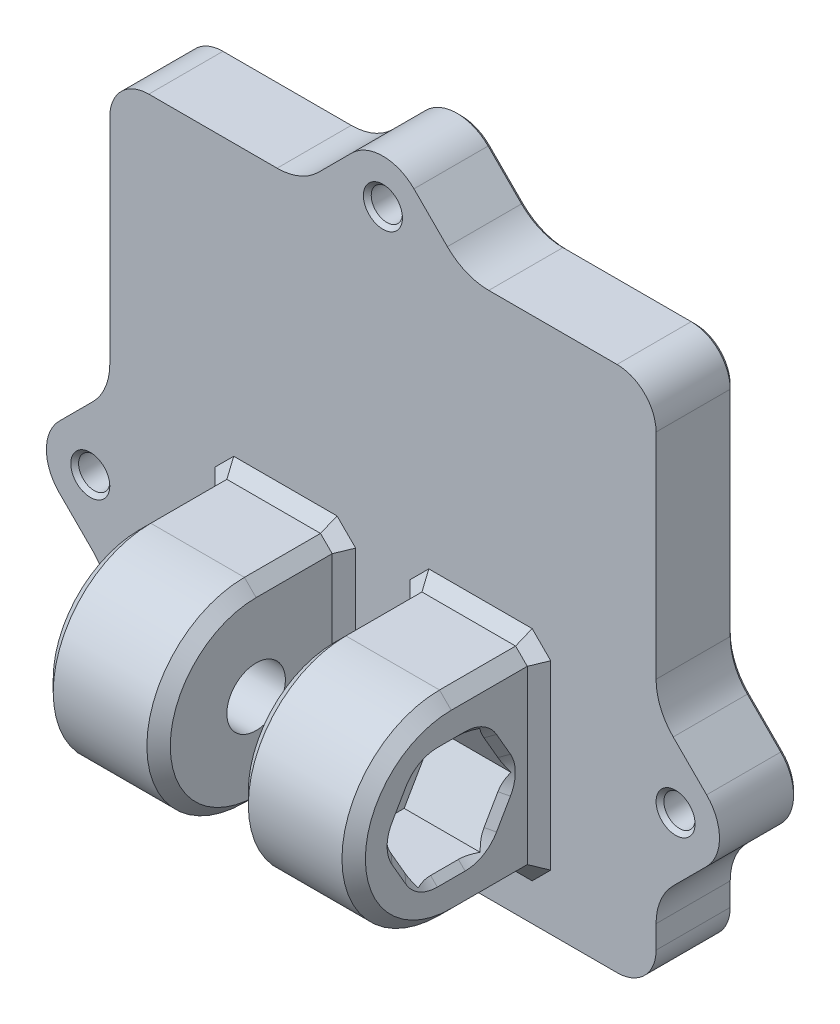
SolidWorks part; units mm, degrees
note: The reader was unsure of these and kept them because the rebuilt part matched: shared geometry of "Sketch13<3>", "Sketch17<3>", "Sketch17<4>", "Sketch17<5>", "Sketch17<6>".
material "POM Acetal Copolymer"
ref_plane "Front" through (0, 0, 0) normal (0, 0, 1) x (1, 0, 0)
ref_plane "Top" through (0, 0, 0) normal (0, 1, 0) x (1, 0, 0)
ref_plane "Right" through (0, 0, 0) normal (1, 0, 0) x (0, 0, -1)
sketch "Sketch13" plane through (0, 0, 0) normal (0, 0, 1) x (1, 0, 0)
  line L0 (-5.4246, -1) -> (-12, -1)
  line L1 (-14, -3) -> (-14, -13.9754)
  line L2 (-14, -24.8246) -> (-14, -26)
  line L3 (7.35, -3.5) -> (6.1644, -3.5) construction
  line L4 (7.75, -3.9) -> (7.75, -4.575) construction
  line L5 (-11.15, -28) -> (-11.15, -25.74) construction
  line L6 (-11.9, -24.5) -> (-11.9, -20.075) construction
  line L7 (-11.5, -19.675) -> (-10.35, -19.675) construction
  line L8 (-10.35, -14.475) -> (-11.5, -14.475) construction
  line L9 (-11.9, -14.075) -> (-11.9, -7.575) construction
  line L10 (-11.5, -7.175) -> (-10.65, -7.175) construction
  line L11 (7.35, -2.9) -> (6.1644, -2.9) construction
  line L12 (12, -28) -> (-12, -28)
  line L13 (1.591, 1.591) -> (3.3033, -0.1213)
  line L14 (-8.05, -3.9) -> (-8.05, -4.575) construction
  line L15 (0, 0) -> (0, -10) construction
  line L16 (-1.591, 1.591) -> (-3.3033, -0.1213)
  line L17 (11.5, -7.175) -> (10.35, -7.175) construction
  line L18 (11.9, -14.075) -> (11.9, -7.575) construction
  line L19 (10.15, -14.475) -> (11.5, -14.475) construction
  line L20 (11.5, -19.675) -> (10.15, -19.675) construction
  line L21 (11.9, -24.5) -> (11.9, -20.075) construction
  line L22 (11.15, -28) -> (11.15, -25.74) construction
  line L23 (10.5, -25.9) -> (-10.5, -25.9) construction
  line L24 (14, -24.8246) -> (14, -26)
  line L25 (14, -3) -> (14, -13.9754)
  line L26 (5.4246, -1) -> (12, -1)
  line L27 (7.35, -2.9) -> (-7.65, -2.9)
  line L28 (8.35, -3.9) -> (8.35, -4.575)
  line L29 (11.5, -6.575) -> (10.35, -6.575)
  line L30 (12.5, -14.075) -> (12.5, -7.575)
  line L31 (10.15, -15.075) -> (11.5, -15.075)
  line L32 (11.5, -19.075) -> (10.15, -19.075)
  line L33 (12.5, -24.5) -> (12.5, -20.075)
  line L34 (10.5, -26.5) -> (-10.5, -26.5)
  line L35 (-12.5, -24.5) -> (-12.5, -20.075)
  line L36 (-11.5, -19.075) -> (-10.35, -19.075)
  line L37 (-10.35, -15.075) -> (-11.5, -15.075)
  line L38 (-12.5, -14.075) -> (-12.5, -7.575)
  line L39 (-11.5, -6.575) -> (-10.65, -6.575)
  line L40 (-8.65, -3.9) -> (-8.65, -4.575)
  line L41 (-16.591, -17.809) -> (-14.8787, -16.0967)
  line L42 (-16.591, -20.991) -> (-14.8787, -22.7033)
  line L43 (-15, -19.4) -> (-13.0372, -19.4) construction
  line L44 (16.591, -20.991) -> (14.8787, -22.7033)
  line L45 (16.591, -17.809) -> (14.8787, -16.0967)
  line L46 (12.45, -2.475) -> (12.45, -26.525) construction
  line L47 (12.45, -26.525) -> (-12.45, -26.525) construction
  line L48 (-12.45, -26.525) -> (-12.45, -2.475) construction
  line L49 (-12.45, -2.475) -> (12.45, -2.475) construction
  line L50 (5.1303, -14.5) -> (-6.4544, -14.5) construction
  arc A0 (-12, -1) -> (-14, -3) centre (-12, -3) ccw
  arc A1 (-14.8787, -22.7033) -> (-14, -24.8246) centre (-17, -24.8246) cw
  arc A2 (-16.591, -17.809) -> (-16.591, -20.991) centre (-15, -19.4) ccw
  arc A3 (-14.8787, -16.0967) -> (-14, -13.9754) centre (-17, -13.9754) ccw
  arc A4 (-14, -26) -> (-12, -28) centre (-12, -26) ccw
  circle A5 centre (0, 0) radius 0.8
  circle A6 centre (15, -19.4) radius 0.8
  arc A7 (1.591, 1.591) -> (-1.591, 1.591) centre (0, 0) ccw
  arc A8 (-3.3033, -0.1213) -> (-5.4246, -1) centre (-5.4246, 2) cw
  arc A9 (-10.5, -25.9) -> (-11.9, -24.5) centre (-10.5, -24.5) cw construction
  arc A10 (-11.9, -20.075) -> (-11.5, -19.675) centre (-11.5, -20.075) cw construction
  arc A11 (-10.35, -19.675) -> (-10.35, -14.475) centre (-10.35, -17.075) ccw construction
  arc A12 (-11.5, -14.475) -> (-11.9, -14.075) centre (-11.5, -14.075) cw construction
  arc A13 (-11.9, -7.575) -> (-11.5, -7.175) centre (-11.5, -7.575) cw construction
  arc A14 (-10.65, -7.175) -> (-8.05, -4.575) centre (-10.65, -4.575) ccw construction
  arc A15 (-8.05, -3.9) -> (-7.65, -3.5) centre (-7.65, -3.9) cw construction
  circle A16 centre (-15, -19.4) radius 0.8
  circle A17 centre (-10.35, -17.075) radius 1.05
  circle A18 centre (-10.65, -4.575) radius 1.05
  circle A19 centre (10.15, -17.075) radius 1.05
  circle A20 centre (10.35, -4.575) radius 1.05
  arc A21 (7.75, -3.9) -> (7.35, -3.5) centre (7.35, -3.9) ccw construction
  arc A22 (10.35, -7.175) -> (7.75, -4.575) centre (10.35, -4.575) cw construction
  arc A23 (11.9, -7.575) -> (11.5, -7.175) centre (11.5, -7.575) ccw construction
  arc A24 (11.5, -14.475) -> (11.9, -14.075) centre (11.5, -14.075) ccw construction
  arc A25 (10.15, -19.675) -> (10.15, -14.475) centre (10.15, -17.075) cw construction
  arc A26 (11.9, -20.075) -> (11.5, -19.675) centre (11.5, -20.075) ccw construction
  arc A27 (10.5, -25.9) -> (11.9, -24.5) centre (10.5, -24.5) ccw construction
  arc A28 (14, -26) -> (12, -28) centre (12, -26) cw
  arc A30 (16.591, -17.809) -> (16.591, -20.991) centre (15, -19.4) cw
  arc A32 (12, -1) -> (14, -3) centre (12, -3) cw
  arc A33 (3.3033, -0.1213) -> (5.4246, -1) centre (5.4246, 2) ccw
  arc A34 (-1.591, 1.591) -> (1.591, 1.591) centre (0, 0) cw
  arc A35 (8.35, -3.9) -> (7.35, -2.9) centre (7.35, -3.9) ccw
  arc A36 (10.35, -6.575) -> (8.35, -4.575) centre (10.35, -4.575) cw
  arc A37 (12.5, -7.575) -> (11.5, -6.575) centre (11.5, -7.575) ccw
  arc A38 (11.5, -15.075) -> (12.5, -14.075) centre (11.5, -14.075) ccw
  arc A39 (10.15, -19.075) -> (10.15, -15.075) centre (10.15, -17.075) cw
  arc A40 (12.5, -20.075) -> (11.5, -19.075) centre (11.5, -20.075) ccw
  arc A41 (10.5, -26.5) -> (12.5, -24.5) centre (10.5, -24.5) ccw
  arc A42 (-10.5, -26.5) -> (-12.5, -24.5) centre (-10.5, -24.5) cw
  arc A43 (-12.5, -20.075) -> (-11.5, -19.075) centre (-11.5, -20.075) cw
  arc A44 (-10.35, -19.075) -> (-10.35, -15.075) centre (-10.35, -17.075) ccw
  arc A45 (-11.5, -15.075) -> (-12.5, -14.075) centre (-11.5, -14.075) cw
  arc A46 (-12.5, -7.575) -> (-11.5, -6.575) centre (-11.5, -7.575) cw
  arc A47 (-10.65, -6.575) -> (-8.65, -4.575) centre (-10.65, -4.575) ccw
  arc A48 (-8.65, -3.9) -> (-7.65, -2.9) centre (-7.65, -3.9) cw
  arc A49 (14.8787, -22.7033) -> (14, -24.8246) centre (17, -24.8246) ccw
  arc A50 (14.8787, -16.0967) -> (14, -13.9754) centre (17, -13.9754) cw
  dimension "D3" = 1.6
  dimension "D4" = 2.25
  dimension "D7" = 3
  dimension "D8" = 2
  dimension "D14" = 1.4
  dimension "D15" = 2.1
  dimension "D19" = 2.6
  dimension "D20" = 0.4
  dimension "D27" = 3
  dimension "D31" = 20.5
  dimension "D5" = 2.9
  dimension "D6" = 1
  dimension "D9" = 28
  dimension "D10" = 2.1
  dimension "D11" = 27
  dimension "D12" = 0.75
  dimension "D13" = 0.6
  dimension "D16" = 2.1
  dimension "D17" = 2.1
  dimension "D18" = 1.8
  dimension "D21" = 1
  dimension "D22" = 19.4
  dimension "D23" = 2.1
  dimension "D24" = 90
  dimension "D25" = 10
  dimension "D26" = 90
  dimension "D28" = 24.9
  dimension "D29" = 24.05
  dimension "D30" = 21
  dimension "D32" = 12.5
extrude "Boss-Extrude3" add sketch "Sketch13" along normal blind 4 separate body
sketch "Sketch14" plane through (0, 0, 4) normal (0, 0, 1) x (1, 0, 0)
  line L0 (-5.4246, -1) -> (-12, -1) construction
  line L1 (12, -1) -> (0.3202, -1)
  line L2 (-14, -3) -> (-14, -13.9754) construction
  line L3 (-14, -3) -> (-14, -19.0798)
  line L5 (14, -3) -> (14, -13.9754) construction
  line L6 (14, -3) -> (14, -19.0798)
  line L8 (12, -28) -> (-12, -28) construction
  line L9 (12, -28) -> (-12, -28)
  line L10 (-0.3202, -1) -> (-12, -1)
  line L11 (14, -19.7202) -> (14, -26)
  line L12 (-14, -19.7202) -> (-14, -26)
  arc A0 (-12, -1) -> (-14, -3) centre (-12, -3) ccw construction
  arc A1 (-12, -1) -> (-14, -3) centre (-12, -3) ccw
  arc A2 (14, -3) -> (12, -1) centre (12, -3) ccw construction
  arc A3 (14, -3) -> (12, -1) centre (12, -3) ccw
  arc A4 (12, -28) -> (14, -26) centre (12, -26) ccw construction
  arc A5 (12, -28) -> (14, -26) centre (12, -26) ccw
  arc A6 (-14, -26) -> (-12, -28) centre (-12, -26) ccw construction
  arc A7 (-14, -26) -> (-12, -28) centre (-12, -26) ccw
  arc A9 (-14, -19.7202) -> (-14, -19.0798) centre (-15, -19.4) ccw
  arc A11 (14, -19.0798) -> (14, -19.7202) centre (15, -19.4) ccw
  arc A13 (0.3202, -1) -> (-0.3202, -1) centre (0, 0) cw
  circle A14 centre (0, 0) radius 0.8 construction
  circle A15 centre (-15, -19.4) radius 0.8 construction
  circle A16 centre (15, -19.4) radius 0.8 construction
  dimension "D1" = 1.05
extrude "Boss-Extrude4" add sketch "Sketch14" against normal blind 1
extrude "Cut-Extrude10" cut sketch "Sketch13<3>" along normal blind 1 contours A20 | A18 | A17 | A19
sketch "Sketch13<3>" plane through (0, 0, 0) normal (0, 0, 1) x (1, 0, 0) same geometry as "Sketch13"
chamfer "Chamfer3" distance 0.6 angle 45 28 edges at (0, -26.5, 3) (11.9142, -25.9142, 3) (-11.9142, -25.9142, 3) (12.5, -22.2875, 3) (-12.5, -22.2875, 3) (12.2071, -19.3679, 3) (-12.2071, -19.3679, 3) (10.825, -19.075, 3) (-10.925, -19.075, 3) (8.15, -17.075, 3) (-8.35, -17.075, 3) (10.825, -15.075, 3) (-10.925, -15.075, 3) (12.2071, -14.7821, 3) (-12.2071, -14.7821, 3) (12.5, -10.825, 3) (-12.5, -10.825, 3) (12.2071, -6.8679, 3) (-12.2071, -6.8679, 3) (10.925, -6.575, 3) (-11.075, -6.575, 3) (8.9358, -5.9892, 3) (-9.2358, -5.9892, 3) (8.35, -4.2375, 3) (-8.65, -4.2375, 3) (8.0571, -3.1929, 3) (-8.3571, -3.1929, 3) (-0.15, -2.9, 3)
sketch "Sketch15" plane through (0, -28, 0) normal (0, -1, 0) x (1, 0, 0)
  line L0 (-11.15, 0) -> (-11.15, 2.6)
  line L1 (12, 0) -> (-12, 0) construction
  line L2 (-11.15, 2.6) -> (11.15, 2.6)
  line L3 (11.15, 2.6) -> (11.15, 0)
  line L4 (11.15, 0) -> (-11.15, 0)
  dimension "D1" = 2.6
extrude "Cut-Extrude7" cut sketch "Sketch15" against normal up to next
sketch "Sketch16" plane through (0, 0, 2.6) normal (0, 0, -1) x (-1, 0, 0)
  line L0 (10.5, -26.3) -> (-10.5, -26.3) construction
  line L1 (10.5, -26.3) -> (-10.5, -26.3)
  line L2 (-10.5, -25.9) -> (10.5, -25.9) construction
  line L3 (-10.5, -25.9) -> (10.5, -25.9)
  line L4 (11.15, -26.1785) -> (11.15, -25.74)
  line L5 (-11.15, -26.1785) -> (-11.15, -25.74)
  arc A0 (-11.15, -26.1785) -> (-10.5, -26.3) centre (-10.5, -24.5) ccw construction
  arc A1 (-11.15, -26.1785) -> (-10.5, -26.3) centre (-10.5, -24.5) ccw
  arc A2 (-11.9, -24.5) -> (-10.5, -25.9) centre (-10.5, -24.5) ccw construction
  arc A3 (-11.15, -25.74) -> (-10.5, -25.9) centre (-10.5, -24.5) ccw
  arc A4 (10.5, -25.9) -> (11.9, -24.5) centre (10.5, -24.5) ccw construction
  arc A5 (10.5, -25.9) -> (11.15, -25.74) centre (10.5, -24.5) ccw
  arc A6 (10.5, -26.3) -> (11.15, -26.1785) centre (10.5, -24.5) ccw construction
  arc A7 (10.5, -26.3) -> (11.15, -26.1785) centre (10.5, -24.5) ccw
extrude "Cut-Extrude8" cut sketch "Sketch16" against normal up to surface (0.4 mm away) up to face at (-0.0571, -13.3866, 3)
chamfer "Chamfer4" distance 0.2 angle 45 64 edges at (-14.2, -19.4, 4) (-14.2, -19.4, 0) (15.8, -19.4, 4) (15.8, -19.4, 0) (0.8, 0, 4) (0.8, 0, 0) (12.1279, -25.6619, 0) (-12.1279, -25.6619, 0) (12.5, -22.2875, 0) (-12.5, -22.2875, 0) (12.2071, -19.3679, 0) (-12.2071, -19.3679, 0) (10.825, -19.075, 0) (-10.925, -19.075, 0) (8.15, -17.075, 0) (-8.35, -17.075, 0) (10.825, -15.075, 0) (-10.925, -15.075, 0) (12.2071, -14.7821, 0) (-12.2071, -14.7821, 0) (12.5, -10.825, 0) (-12.5, -10.825, 0) (12.2071, -6.8679, 0) (-12.2071, -6.8679, 0) (10.925, -6.575, 0) (-11.075, -6.575, 0) (8.9358, -5.9892, 0) (-9.2358, -5.9892, 0) (8.35, -4.2375, 0) (-8.65, -4.2375, 0) (8.0571, -3.1929, 0) (-8.3571, -3.1929, 0) (-0.15, -2.9, 0) (11.575, -28, 0) (13.4142, -27.4142, 0) (14, -25.4123, 0) (17.25, -19.4, 0) (14, -8.4877, 0) (13.4142, -1.5858, 0) (8.7123, -1, 0) (0, 2.25, 0) (-8.7123, -1, 0) (-13.4142, -1.5858, 0) (-14, -8.4877, 0) (-11.575, -28, 0) (-13.4142, -27.4142, 0) (-17.25, -19.4, 0) (-14, -25.4123, 0) (11.2, -17.075, 0) (-9.3, -17.075, 0) (-9.6, -4.575, 0) (11.4, -4.575, 0) (14.2284, -23.6766, 0) (15.7348, -21.8471, 0) (15.7348, -16.9529, 0) (14.2284, -15.1234, 0) (4.2766, -0.7716, 0) (2.4471, 0.7348, 0) (-2.4471, 0.7348, 0) (-4.2766, -0.7716, 0) (-14.2284, -15.1234, 0) (-15.7348, -16.9529, 0) (-15.7348, -21.8471, 0) (-14.2284, -23.6766, 0)
sketch "Sketch17" plane through (-14, 0, 0) normal (-1, 0, 0) x (0, 0, 1)
  line L1 (4, -15.5) -> (8.5, -15.5)
  line L2 (8.5, -25.5) -> (4, -25.5)
  line L3 (4, -1) -> (0.2, -1) construction
  line L4 (4, -25.5) -> (4, -15.5)
  line L5 (11.6754, -20.5) -> (10.0877, -17.75)
  line L6 (10.0877, -17.75) -> (6.9123, -17.75)
  line L7 (6.9123, -17.75) -> (5.3246, -20.5)
  line L8 (5.3246, -20.5) -> (6.9123, -23.25)
  line L9 (6.9123, -23.25) -> (10.0877, -23.25)
  line L10 (10.0877, -23.25) -> (11.6754, -20.5)
  line L11 (11.536, -19.5694) -> (10.8239, -18.3361)
  line L12 (9.2121, -17.4054) -> (7.7879, -17.4054)
  line L13 (6.1761, -18.3361) -> (5.464, -19.5694)
  line L14 (5.464, -21.4306) -> (6.1761, -22.6639)
  line L15 (7.7879, -23.5946) -> (9.2121, -23.5946)
  line L16 (10.8239, -22.6639) -> (11.536, -21.4306)
  line L17 (8.5, -20.5) -> (0.8012, -20.5) construction
  line L19 (4, -3) -> (4, -13.9754) construction
  arc A0 (8.5, -15.5) -> (8.5, -25.5) centre (8.5, -20.5) cw
  circle A1 centre (8.5, -20.5) radius 2.75
  circle A2 centre (8.5, -20.5) radius 1.5
  arc A3 (10.8239, -18.3361) -> (9.2121, -17.4054) centre (9.2121, -19.2667) ccw
  arc A4 (7.7879, -17.4054) -> (6.1761, -18.3361) centre (7.7879, -19.2667) ccw
  arc A5 (5.464, -19.5694) -> (5.464, -21.4306) centre (7.0759, -20.5) ccw
  arc A6 (6.1761, -22.6639) -> (7.7879, -23.5946) centre (7.7879, -21.7333) ccw
  arc A7 (9.2121, -23.5946) -> (10.8239, -22.6639) centre (9.2121, -21.7333) ccw
  arc A8 (11.536, -21.4306) -> (11.536, -19.5694) centre (9.9241, -20.5) ccw
  circle A9 centre (8.5, -20.5) radius 1.4241 construction
  circle A10 centre (8.5, -20.5) radius 3.1754 construction
  dimension "D3" = 3
  dimension "D4" = 5
  dimension "D5" = 5.5
  dimension "D7" = 5.5
  dimension "D1" = 19.5
  dimension "D2" = 4.5
  dimension "D6" = 6.1891
extrude "Boss-Extrude5" add sketch "Sketch17" along normal mid plane 16 from offset 14 contours A0 L2 L4 L1 offset against normal yes
sketch "Sketch18" plane through (0, -15.5, 0) normal (0, 1, 0) x (1, 0, 0)
  line L0 (0, -4) -> (0, -14.3974) construction
  line L2 (-8, -13.5) -> (8, -13.5) construction
  line L3 (-2, -4) -> (2, -4)
  line L4 (-2, -4) -> (-2, -13.5)
  line L5 (-2, -13.5) -> (2, -13.5)
  line L6 (2, -4) -> (2, -13.5)
  line L7 (-8, -4) -> (8, -4) construction
  line L8 (-8, -4) -> (8, -4) construction
  dimension "D1" = 4
extrude "Cut-Extrude11" cut sketch "Sketch18" against normal through all
extrude "Cut-Extrude13" cut sketch "Sketch17<3>" against normal blind 2.5 from vertex at -6 contours A1 A2 | A2 starting at point (-8, -15.5, 8.5)
sketch "Sketch17<3>" plane through (-14, 0, 0) normal (-1, 0, 0) x (0, 0, 1) same geometry as "Sketch17"
extrude "Cut-Extrude14" cut sketch "Sketch17<4>" along normal blind 4 from vertex at -22 contours L9 L10 L5 L6 L7 L8 A1 | A1 A2 | A2 | A1 L10 L5 | A1 L9 L10 | A1 L7 L8 | A1 L6 L7 | A1 L8 L9 starting at point (8, -15.5, 8.5)
sketch "Sketch17<4>" plane through (-14, 0, 0) normal (-1, 0, 0) x (0, 0, 1) same geometry as "Sketch17"
extrude "Cut-Extrude16" cut sketch "Sketch17<5>" along normal blind 1 draft 45 from vertex at -22 contours L16 A8 L11 A3 L12 A4 L13 A5 L14 A6 L15 A7 L10 L9 L8 L7 L6 L5 | L9 L10 L5 L6 L7 L8 A1 | A1 A2 | A1 L6 L7 | A1 L10 L5 | A1 L9 L10 | A1 L8 L9 | A1 L7 L8
sketch "Sketch17<5>" plane through (-14, 0, 0) normal (-1, 0, 0) x (0, 0, 1) same geometry as "Sketch17"
chamfer "Chamfer5" distance 0.6 angle 45 12 edges at (-2, -15.5, 6.25) (-2, -25.5, 6.25) (-2, -20.5, 13.5) (2, -25.5, 6.25) (2, -15.5, 6.25) (2, -20.5, 13.5) (-8, -15.5, 6.25) (-8, -25.5, 6.25) (-8, -20.5, 13.5) (8, -25.5, 6.25) (8, -20.5, 13.5) (8, -15.5, 6.25)
chamfer "Chamfer6" distance 0.6 angle 45 16 edges at (-2.3, -15.8, 4) (-5, -15.5, 4) (-5, -25.5, 4) (-2.3, -25.2, 4) (-2, -20.5, 4) (5, -15.5, 4) (2.3, -15.8, 4) (2, -20.5, 4) (2.3, -25.2, 4) (5, -25.5, 4) (-8, -20.5, 4) (8, -20.5, 4) (-7.7, -15.8, 4) (-7.7, -25.2, 4) (7.7, -25.2, 4) (7.7, -15.8, 4)
extrude "Cut-Extrude17" cut sketch "Sketch17<6>" against normal through all contours A2
sketch "Sketch17<6>" plane through (-14, 0, 0) normal (-1, 0, 0) x (0, 0, 1) same geometry as "Sketch17"
chamfer "Chamfer7" distance 0.4 angle 45 1 edges at (-8, -20.5, 11.25)
